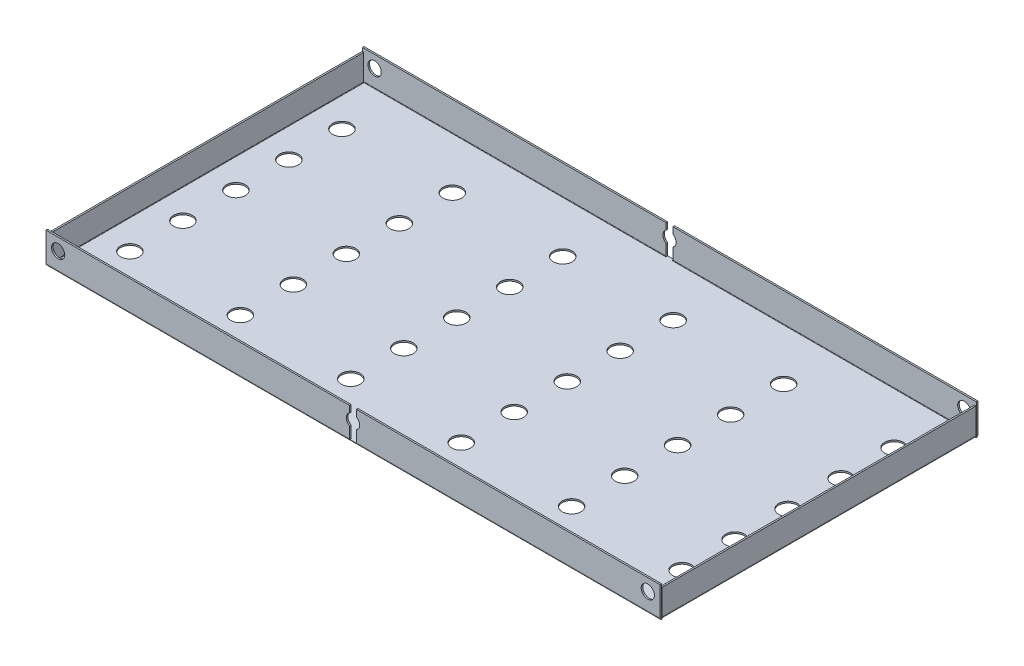
SolidWorks part; units mm, degrees
note: The reader was unsure of these and kept them because the rebuilt part matched: flange length of "边线-法兰1", "边线-法兰2".
ref_plane "前视基准面" through (0, 0, 0) normal (0, 0, 1) x (1, 0, 0)
ref_plane "上视基准面" through (0, 0, 0) normal (0, 1, 0) x (1, 0, 0)
ref_plane "右视基准面" through (0, 0, 0) normal (1, 0, 0) x (0, 0, -1)
sketch "草图1" plane through (0, 0, 0) normal (0, 1, 0) x (1, 0, 0)
  line L0 (-100, 72) -> (-100, -72) construction
  line L1 (-139, 72) -> (139, 72)
  line L2 (-139, 72) -> (-139, -72)
  line L3 (-139, -72) -> (139, -72)
  line L5 (-139, -72) -> (139, 72) construction
  line L6 (-139, 72) -> (139, -72) construction
  line L7 (-50, 72) -> (-50, -72) construction
  line L8 (0, 0) -> (0, -72) construction
  line L10 (139, 72) -> (139, -72)
  circle A0 centre (-125, -48) radius 4.25
  circle A1 centre (-125, -24) radius 4.25
  circle A2 centre (-125, 0) radius 4.25
  circle A3 centre (-125, 24) radius 4.25
  circle A4 centre (-125, 48) radius 4.25
  circle A5 centre (-75, -48) radius 4.25
  circle A6 centre (-75, -24) radius 4.25
  circle A7 centre (-75, 0) radius 4.25
  circle A8 centre (-75, 24) radius 4.25
  circle A9 centre (-75, 48) radius 4.25
  circle A40 centre (-25, -48) radius 4.25
  circle A41 centre (-25, -24) radius 4.25
  circle A42 centre (-25, 0) radius 4.25
  circle A43 centre (-25, 24) radius 4.25
  circle A44 centre (-25, 48) radius 4.25
  circle A45 centre (25, -48) radius 4.25
  circle A46 centre (25, -24) radius 4.25
  circle A47 centre (25, 0) radius 4.25
  circle A48 centre (25, 24) radius 4.25
  circle A49 centre (25, 48) radius 4.25
  circle A50 centre (75, 48) radius 4.25
  circle A51 centre (75, 24) radius 4.25
  circle A52 centre (75, 0) radius 4.25
  circle A53 centre (75, -24) radius 4.25
  circle A54 centre (75, -48) radius 4.25
  circle A55 centre (125, -48) radius 4.25
  circle A56 centre (125, -24) radius 4.25
  circle A57 centre (125, 0) radius 4.25
  circle A58 centre (125, 24) radius 4.25
  circle A59 centre (125, 48) radius 4.25
  point P0 (0, 0)
  dimension "D5" = 8.5
  dimension "D6" = 24
  dimension "D18" = 278
  dimension "D2" = 144
  dimension "D3" = 24
  dimension "D4" = 14
  dimension "D7" = 24
  dimension "D8" = 24
  dimension "D9" = 24
  dimension "D10" = 24
  dimension "D14" = 25
  dimension "D15" = 50
  dimension "D16" = 50
base flange "基体-法兰1" sketch "草图1" thickness 0.7 reverse thickness direction no parameters "D1"=0.2
edge flange "边线-法兰1" sketch "草图12" flange profiles "草图12", "草图13" flange angle 90 flange length 14 flange position material inside bend radius 0.2 thickness 0.7 relief rectangular parameters "D6"=10, "D8"=1
sketch "草图12" plane through (0, 0, 72) normal (0, 0, 1) x (1, 0, 0)
  line L2 (-139, 0) -> (-139, 13.3)
  line L3 (-139, 13.3) -> (139, 13.3)
  line L4 (139, 13.3) -> (139, 0)
  line L11 (-139, 0) -> (139, 0) construction
  line L12 (-139, 0) -> (139, 0)
sketch "草图13" plane through (0, 0, -72) normal (0, 0, -1) x (-1, 0, 0)
  line L2 (-139, 0) -> (-139, 13.3)
  line L3 (-139, 13.3) -> (139, 13.3)
  line L4 (139, 13.3) -> (139, 0)
  line L7 (-139, 0) -> (139, 0) construction
  line L8 (-139, 0) -> (139, 0)
bend "边线折弯1" bend radius 0.2 bend angle 90 parameters "D5"=1
bend "边线折弯2" bend radius 0.2 bend angle 90 parameters "D5"=2
sketch "草图14" plane through (0, 0, 71.3) normal (0, 0, -1) x (-1, 0, 0)
  line L0 (0, 13.3) -> (0, 0) construction
  line L1 (139, 13.3) -> (-139, 13.3) construction
  line L2 (-139, 13.3) -> (-139, 0.2) construction
  circle A0 centre (-133.5, 7.8) radius 3
  circle A1 centre (0, 7.8) radius 3
  circle A2 centre (133.5, 7.8) radius 3
  dimension "D1" = 6
  dimension "D2" = 5.5
  dimension "D3" = 5.5
  dimension "D4" = 5.5
  dimension "D5" = 6
extrude "切除-拉伸1" cut sketch "草图14" against normal blind 10
sketch "草图15" plane through (0, 0, -72) normal (0, 0, -1) x (-1, 0, 0)
  line L0 (0, 13.3) -> (0, 0) construction
  line L1 (139, 13.3) -> (-139, 13.3) construction
  line L2 (-139, 13.3) -> (-139, 0.2) construction
  circle A0 centre (-133.5, 7.8) radius 3
  circle A1 centre (0, 7.8) radius 3
  circle A2 centre (133.5, 7.8) radius 3
  dimension "D1" = 6
  dimension "D2" = 5.5
  dimension "D3" = 6
  dimension "D4" = 5.5
  dimension "D5" = 5.5
extrude "切除-拉伸2" cut sketch "草图15" against normal blind 10
sketch "草图16" plane through (0, 0, -72) normal (0, 0, -1) x (-1, 0, 0)
  line L0 (0, 0) -> (0, 13.3) construction
  line L1 (139, 13.3) -> (-139, 13.3) construction
  line L2 (1.5, 0) -> (1.5, 13.3)
  line L3 (-1.5, 0) -> (-1.5, 13.3)
  line L4 (-1.5, 13.3) -> (1.5, 13.3)
  line L5 (-1.5, 0) -> (1.5, 0)
  dimension "D1" = 1.5
  dimension "D2" = 1.5
extrude "切除-拉伸3" cut sketch "草图16" against normal blind 10
sketch "草图17" plane through (0, 0, 72) normal (0, 0, 1) x (1, 0, 0)
  line L0 (0, 0) -> (0, 13.3) construction
  line L1 (139, 13.3) -> (-139, 13.3) construction
  line L2 (1.5, 0) -> (1.5, 13.3)
  line L3 (-1.5, 0) -> (-1.5, 13.3)
  line L4 (-1.5, 13.3) -> (1.5, 13.3)
  line L5 (-1.5, 0) -> (1.5, 0)
  dimension "D1" = 1.5
  dimension "D2" = 1.5
extrude "切除-拉伸4" cut sketch "草图17" against normal blind 10
edge flange "边线-法兰2" sketch "草图22" flange profiles "草图22", "草图23" flange angle 90 flange length 12.5 flange position material inside bend radius 0.2 thickness 0.7 relief none parameters "D6"=10, "D8"=1
sketch "草图22" plane through (-139, 0, 0) normal (-1, 0, 0) x (0, 0, 1)
  line L2 (-71.1, 0) -> (-71.1, 11.8)
  line L3 (-71.1, 11.8) -> (71.1, 11.8)
  line L4 (71.1, 11.8) -> (71.1, 0)
  line L11 (-71.1, 0) -> (71.1, 0) construction
  line L12 (-71.1, 0) -> (71.1, 0)
sketch "草图23" plane through (139, 0, 0) normal (1, 0, 0) x (0, 0, -1)
  line L2 (71.1, 0) -> (71.1, 11.8)
  line L3 (71.1, 11.8) -> (-71.1, 11.8)
  line L4 (-71.1, 11.8) -> (-71.1, 0)
  line L9 (-71.1, 0) -> (71.1, 0) construction
  line L10 (-71.1, 0) -> (71.1, 0)
bend "边线折弯3" bend radius 0.2 bend angle 90 parameters "D5"=3
bend "边线折弯4" bend radius 0.2 bend angle 90 parameters "D5"=4
sketch "折弯-线1" [suppressed] plane through (0, 0, 0) normal (0, 1, 0) x (1, 0, 0)
sketch "边界框1" [suppressed] plane through (0, 0, 0) normal (0, 1, 0) x (1, 0, 0)
sheet metal parameters "钣金6" thickness 0.7 parameters "D1"=0.2
flat pattern "平板型式6" [suppressed]
sketch "折弯-线2" plane through (0, 0, 0) normal (0, 1, 0) x (1, 0, 0)
sketch3d "边界框2" [suppressed]
  line L0 (200, -72, 0) -> (-200, -72, 0) construction
  line L1 (200, 72, 0) -> (-200, 72, 0) construction
  line L2 (200, -72, 0) -> (200, 72, 0) construction
  line L3 (-200, -72, 0) -> (-200, 72, 0) construction
sheet metal parameters "钣金7" thickness 0.7 parameters "D1"=0.2
flat pattern "平板型式6" [suppressed]
sketch "折弯-线2" plane through (0, 0, 0) normal (0, 1, 0) x (1, 0, 0)
sketch3d "边界框2" [suppressed]
  line L0 (200, -72, 0) -> (-200, -72, 0) construction
  line L1 (200, 72, 0) -> (-200, 72, 0) construction
  line L2 (200, -72, 0) -> (200, 72, 0) construction
  line L3 (-200, -72, 0) -> (-200, 72, 0) construction
bend of the flat pattern "展平-<边线折弯1>1"
bend of the flat pattern "展平-<边线折弯2>1"
sheet metal parameters "钣金8" thickness 0.7 parameters "D1"=0.2
flat pattern "平板型式6" [suppressed]
sketch "折弯-线2" plane through (0, 0, 0) normal (0, 1, 0) x (1, 0, 0)
sketch3d "边界框2" [suppressed]
  line L0 (200, -72, 0) -> (-200, -72, 0) construction
  line L1 (200, 72, 0) -> (-200, 72, 0) construction
  line L2 (200, -72, 0) -> (200, 72, 0) construction
  line L3 (-200, -72, 0) -> (-200, 72, 0) construction
bend of the flat pattern "展平-<边线折弯1>1"
bend of the flat pattern "展平-<边线折弯2>1"
sheet metal parameters "钣金9" thickness 0.7 parameters "D1"=0.2
flat pattern "平板型式6" [suppressed]
sketch "折弯-线2" plane through (0, 0, 0) normal (0, 1, 0) x (1, 0, 0)
sketch3d "边界框2" [suppressed]
  line L0 (200, -72, 0) -> (-200, -72, 0) construction
  line L1 (200, 72, 0) -> (-200, 72, 0) construction
  line L2 (200, -72, 0) -> (200, 72, 0) construction
  line L3 (-200, -72, 0) -> (-200, 72, 0) construction
bend of the flat pattern "展平-<边线折弯1>1"
bend of the flat pattern "展平-<边线折弯2>1"
sheet metal parameters "钣金10" thickness 0.7 parameters "D1"=0.2
flat pattern "平板型式6" [suppressed]
sketch "折弯-线2" plane through (0, 0, 0) normal (0, 1, 0) x (1, 0, 0)
sketch3d "边界框2" [suppressed]
  line L0 (200, -72, 0) -> (-200, -72, 0) construction
  line L1 (200, 72, 0) -> (-200, 72, 0) construction
  line L2 (200, -72, 0) -> (200, 72, 0) construction
  line L3 (-200, -72, 0) -> (-200, 72, 0) construction
bend of the flat pattern "展平-<边线折弯1>1"
bend of the flat pattern "展平-<边线折弯2>1"
sheet metal parameters "钣金11" thickness 0.7 parameters "D1"=0.2
flat pattern "平板型式6" [suppressed]
sketch "折弯-线2" plane through (0, 0, 0) normal (0, 1, 0) x (1, 0, 0)
sketch3d "边界框2" [suppressed]
  line L0 (200, -72, 0) -> (-200, -72, 0) construction
  line L1 (200, 72, 0) -> (-200, 72, 0) construction
  line L2 (200, -72, 0) -> (200, 72, 0) construction
  line L3 (-200, -72, 0) -> (-200, 72, 0) construction
bend of the flat pattern "展平-<边线折弯1>1"
bend of the flat pattern "展平-<边线折弯2>1"
sheet metal parameters "钣金12" thickness 0.7 parameters "D1"=0.2
flat pattern "平板型式6"
sketch "折弯-线2" plane through (0, 0, 0) normal (0, 1, 0) x (1, 0, 0)
sketch3d "边界框2" [suppressed]
  line L0 (200, -72, 0) -> (-200, -72, 0) construction
  line L1 (200, 72, 0) -> (-200, 72, 0) construction
  line L2 (200, -72, 0) -> (200, 72, 0) construction
  line L3 (-200, -72, 0) -> (-200, 72, 0) construction
bend of the flat pattern "展平-<边线折弯1>1"
bend of the flat pattern "展平-<边线折弯2>1"
bend of the flat pattern "展平-<边线折弯3>1"
bend of the flat pattern "展平-<边线折弯4>1"
